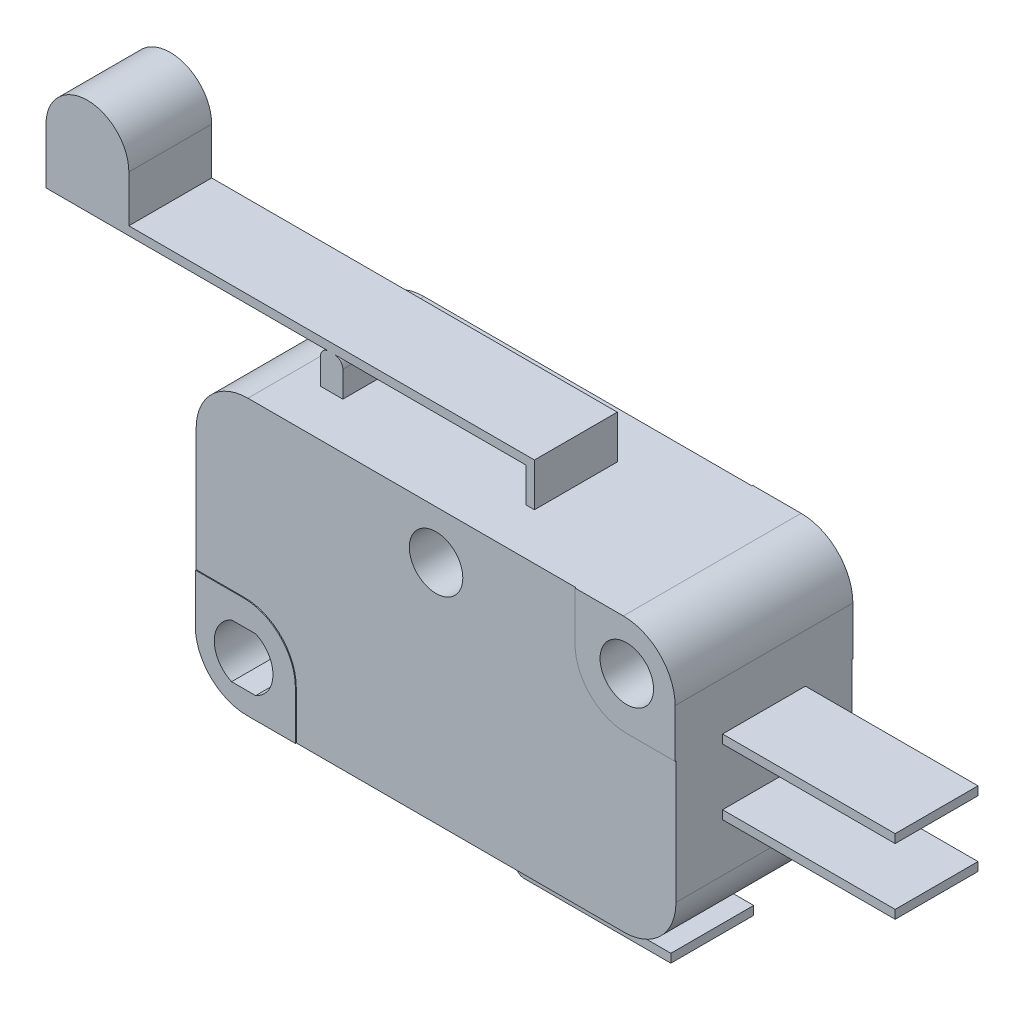
SolidWorks part; units mm, degrees
ref_plane "Front Plane" through (0, 0, 0) normal (0, 0, 1) x (1, 0, 0)
ref_plane "Top Plane" through (0, 0, 0) normal (0, 1, 0) x (1, 0, 0)
ref_plane "Right Plane" through (0, 0, 0) normal (1, 0, 0) x (0, 0, -1)
sketch "Sketch1" plane through (0, 0, 0) normal (0, 0, 1) x (1, 0, 0)
  line L0 (2.1018, 1.25) -> (3.4982, 1.25)
  line L1 (3, 0) -> (24.8, 0)
  line L2 (0, 3) -> (0, 12.9)
  line L3 (3, 15.9) -> (24.8, 15.9)
  line L4 (27.8, 3) -> (27.8, 12.9)
  line L5 (2.1018, 4.35) -> (3.4982, 4.35)
  line L6 (1.1, 2.8) -> (4.5, 2.8) construction
  line L7 (13.9, 15.9) -> (13.9, 0) construction
  line L8 (15.8022, 0) -> (15.8022, -2.4)
  line L9 (16.3022, -2.9) -> (24.8038, -2.9)
  line L10 (24.8038, -2.9) -> (24.8038, -2.4)
  line L11 (24.8038, -2.4) -> (16.3022, -2.4)
  line L12 (16.3022, -2.4) -> (16.3022, 0)
  line L13 (16.3022, -2.4) -> (15.8022, -2.4) construction
  line L14 (27.8, 5.8) -> (37.8, 5.8)
  line L15 (37.8, 5.8) -> (37.8, 6.3)
  line L16 (37.8, 6.3) -> (27.8, 6.3)
  line L17 (27.8, 9.6) -> (37.8, 9.6)
  line L18 (37.8, 9.6) -> (37.8, 10.1)
  line L19 (37.8, 10.1) -> (27.8, 10.1)
  line L20 (27.8, 7.95) -> (37.8, 7.95) construction
  line L21 (32.8, 10.1) -> (32.8, 5.8) construction
  line L22 (5.8, 0) -> (5.8, 2.8)
  line L23 (0, 5.8) -> (2.8, 5.8)
  line L24 (22, 15.9) -> (22, 13.1)
  line L25 (27.8, 10.1) -> (25, 10.1)
  line L26 (4.5, 15.9) -> (4.5, 17.4)
  line L27 (5.8, 15.9) -> (5.8, 17.4)
  line L28 (5, 17.9) -> (5.3, 17.9)
  line L29 (16.4, 15.9) -> (16.4, 17.9)
  line L30 (16.4, 17.9) -> (-6.6, 17.9)
  line L31 (16.9, 15.9) -> (16.9, 18.4)
  line L32 (16.9, 18.4) -> (-6.6, 18.4)
  line L33 (16.4, 17.9) -> (16.9, 17.9) construction
  line L34 (16.4, 17.9) -> (16.4, 18.4) construction
  line L35 (-6.6, 17.9) -> (-6.6, 18.4)
  line L36 (-6.6, 17.9) -> (-11.4, 17.9)
  line L37 (-11.4, 17.9) -> (-11.4, 21.1)
  line L38 (-9, 21.1) -> (-9, 23.5) construction
  line L39 (-6.6, 21.1) -> (-6.6, 18.4)
  arc A0 (3.4982, 1.25) -> (3.4982, 4.35) centre (2.8, 2.8) ccw
  arc A1 (2.1018, 4.35) -> (2.1018, 1.25) centre (2.8, 2.8) ccw
  circle A2 centre (25, 13.1) radius 1.55
  circle A3 centre (13.9, 13.1) radius 1.55
  arc A4 (0, 12.9) -> (3, 15.9) centre (3, 12.9) cw
  arc A5 (24.8, 0) -> (27.8, 3) centre (24.8, 3) ccw
  arc A6 (3, 0) -> (0, 3) centre (3, 3) cw
  arc A7 (24.8, 15.9) -> (27.8, 12.9) centre (24.8, 12.9) cw
  arc A8 (2.8, 5.8) -> (5.8, 2.8) centre (2.8, 2.8) cw
  arc A9 (25, 10.1) -> (22, 13.1) centre (25, 13.1) cw
  arc A10 (15.8022, -2.4) -> (16.3022, -2.9) centre (16.3022, -2.4) ccw
  arc A11 (5.8, 17.4) -> (5.3, 17.9) centre (5.3, 17.4) ccw
  arc A12 (4.5, 17.4) -> (5, 17.9) centre (5, 17.4) cw
  circle A13 centre (-9, 21.1) radius 2.4
  point P35 (32.8, 10.1)
  point P38 (32.8, 7.95)
  point P45 (0, 0)
  point P63 (15.8022, -2.9)
  dimension "D3" = 3.1
  dimension "D5" = 3.1
  dimension "D10" = 18.8
  dimension "D15" = 3
  dimension "D16" = 3
  dimension "D17" = 3
  dimension "D18" = 0.5
  dimension "D19" = 0.5
  dimension "D21" = 34
  dimension "D23" = 4.8
  dimension "D1" = 27.8
  dimension "D2" = 15.9
  dimension "D4" = 3.4
  dimension "D6" = 22.2
  dimension "D7" = 10.3
  dimension "D8" = 2.8
  dimension "D9" = 2.8
  dimension "D11" = 0.5
  dimension "D12" = 11.9978
  dimension "D13" = 9.0017
  dimension "D14" = 37.8
  dimension "D20" = 8.1
  dimension "D22" = 20.7
  dimension "D24" = 2
extrude "Boss-Extrude1" add sketch "Sketch1" along normal blind 5.1 and the other way blind 5.1 contours L25 A9 L24 L3 A4 L2 L23 A8 L22 L1 A5 L4 A3 region at (13.9, 7.8441, 0)
extrude "Boss-Extrude2" add sketch "Sketch1<3>" along normal blind 5.15 and the other way blind 5.15 contours A8 L23 L2 A6 L1 L22 A1 L5 A0 L0 | A9 L25 L4 A7 L3 L24 A2 region at (0.9367, 0.9367, 0) region at (26.4, 10.182, 0)
sketch "Sketch1<3>" plane through (0, 0, 0) normal (0, 0, 1) x (1, 0, 0) same geometry as "Sketch1"
extrude "Boss-Extrude3" add sketch "Sketch1<4>" along normal blind 2.4 and the other way blind 2.4 contours A13 | L35 L30 L28 L29 L3 L31 L32 | A12 L26 L3 L27 A11 L28 | L15 L16 L4 L14 | L18 L19 L4 L17 | L8 A10 L9 L10 L11 L12 L1 | A13 L37 L36 L35 L39 region at (16.0522, -0.0946, 0) region at (5.15, 16.8618, 0) region at (32.8, 6.05, 0) region at (6.052, 18.052, 0) region at (32.8, 9.85, 0) region at (-9, 18.6666, 0) region at (-9, 21.1, 0)
sketch "Sketch1<4>" plane through (0, 0, 0) normal (0, 0, 1) x (1, 0, 0) same geometry as "Sketch1"
sketch "Sketch2" plane through (0, 0, 2.4) normal (0, 0, 1) x (1, 0, 0)
  line L0 (-9, 23.5) -> (-9, 17.9) construction
  line L1 (5, 17.9) -> (-11.4, 17.9) construction
  arc A0 (-6.6, 21.1) -> (-11.4, 21.1) centre (-9, 21.1) ccw construction
